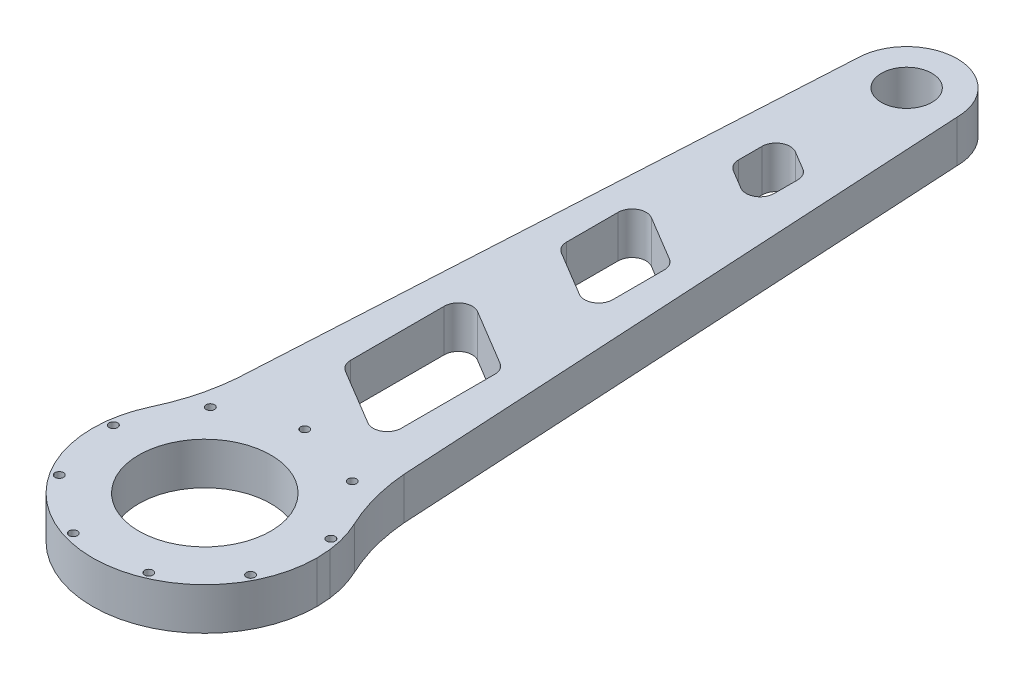
SolidWorks part; units mm, degrees
material "1060 合金"
ref_plane "前视基准面" through (0, 0, 0) normal (0, 0, 1) x (1, 0, 0)
ref_plane "上视基准面" through (0, 0, 0) normal (0, 1, 0) x (1, 0, 0)
ref_plane "右视基准面" through (0, 0, 0) normal (1, 0, 0) x (0, 0, -1)
sketch "草图1" plane through (0, 0, 0) normal (0, 1, 0) x (1, 0, 0)
  line L0 (0, 0) -> (0, 250) construction
  line L1 (-17.9929, -0.504) -> (-24.9902, 249.3)
  line L2 (17.9929, -0.504) -> (24.9902, 249.3)
  line L3 (-11.9953, -0.336) -> (-18.9926, 249.468) construction
  line L4 (11.9953, -0.336) -> (18.9926, 249.468) construction
  line L5 (-16.4444, 158.5) -> (15.7446, 133.5146) construction
  line L6 (15.7446, 133.5146) -> (18.4752, 231) construction
  line L7 (18.4752, 231) -> (-18.0888, 217.2024) construction
  line L8 (-18.0888, 217.2024) -> (-16.4444, 158.5) construction
  line L9 (15.7446, 133.5146) -> (-18.0888, 217.2024) construction
  line L10 (18.5259, 134.639) -> (-15.3075, 218.3268) construction
  line L11 (12.9633, 132.3901) -> (-20.8701, 216.0779) construction
  line L12 (-16.4444, 158.5) -> (-17.7049, 203.5)
  line L13 (-17.7049, 203.5) -> (11.0289, 137.1749)
  line L14 (11.0289, 137.1749) -> (-16.4444, 158.5)
  line L15 (15.9543, 141) -> (18.4752, 231)
  line L16 (-15.3075, 218.3268) -> (-13.7162, 214.3907) construction
  line L17 (18.4752, 231) -> (-12, 219.5)
  line L18 (-12, 219.5) -> (15.9543, 141)
  circle A0 centre (0, 250) radius 25 construction
  circle A1 centre (0, 0) radius 18 construction
  circle A2 centre (0, 0) radius 5.05
  circle A3 centre (0, 250) radius 13
  arc A4 (-17.9929, -0.504) -> (17.9929, -0.504) centre (0, 0) ccw
  arc A5 (-24.9902, 249.3) -> (24.9902, 249.3) centre (0, 250) cw
  arc A6 (-18.9926, 249.468) -> (18.9926, 249.468) centre (0, 250) cw construction
  arc A7 (-11.9953, -0.336) -> (11.9953, -0.336) centre (0, 0) ccw construction
  dimension "D2" = 50
  dimension "D3" = 36
  dimension "D4" = 10.1
  dimension "D5" = 26
  dimension "D1" = 250
  dimension "D9" = 19
  dimension "D10" = 30.5
  dimension "D11" = 16
  dimension "D12" = 45
  dimension "D13" = 90
  dimension "D14" = 12
  dimension "D6" = 6
  dimension "D7" = 3
  dimension "D8" = 3
extrude "凸台-拉伸1" add sketch "草图1" along normal blind 15
fillet "圆角1" radius 3 6 edges at (18.4752, 7.5, -231) (-12, 7.5, -219.5) (-17.7049, 7.5, -203.5) (-16.4444, 7.5, -158.5) (15.9543, 7.5, -141) (11.0289, 7.5, -137.1749)
sketch "草图2" plane through (0, 15, 0) normal (0, 1, 0) x (1, 0, 0)
  line L0 (0, 250) -> (-15, 250) construction
  circle A0 centre (-15, 250) radius 2
  dimension "D2" = 4
  dimension "D1" = 15
extrude "切除-拉伸1" [suppressed] cut sketch "草图2" against normal through all
pattern_circular "阵列(圆周)1" [suppressed] count 3 over 360 reverse direction yes of bodies 107
sketch "草图3" plane through (0, 15, 0) normal (0, 1, 0) x (1, 0, 0)
  line L0 (0, 250) -> (14.25, 250) construction
  circle A0 centre (14.25, 250) radius 2
  dimension "D2" = 4
  dimension "D1" = 14.25
extrude "切除-拉伸2" [suppressed] cut sketch "草图3" against normal through all
pattern_circular "阵列(圆周)2" [suppressed] count 3 over 360 of bodies 109
sketch "草图4" plane through (0, 15, 0) normal (0, 1, 0) x (1, 0, 0)
  line L2 (8.9965, -0.252) -> (15.9937, 249.552)
  line L3 (8.9965, -0.252) -> (15.9937, 249.552) construction
  line L4 (-13.0503, 144.4724) -> (12.4949, 124.6439)
  line L5 (-15.9937, 249.552) -> (-8.9965, -0.252)
  line L6 (-15.9937, 249.552) -> (-8.9965, -0.252) construction
  line L7 (-15.3248, 157.6309) -> (1.7846, 144.3504) construction
  line L8 (12.4949, 124.6439) -> (9.7421, 26.3657)
  line L9 (9.7421, 26.3657) -> (-10.1751, 41.8256)
  line L10 (-10.1751, 41.8256) -> (-13.0503, 144.4724)
  dimension "D3" = 9
  dimension "D1" = 9
  dimension "D2" = 9
extrude "切除-拉伸3" [suppressed] cut sketch "草图4" against normal through all
fillet "圆角2" [suppressed] radius 3
sketch "草图5" plane through (0, 15, 0) normal (0, 1, 0) x (1, 0, 0)
  circle A0 centre (0, 0) radius 27.5
  circle A1 centre (0, 0) radius 5.05
  dimension "D1" = 55
extrude "凸台-拉伸2" [suppressed] add sketch "草图5" against normal up to surface (10 mm away) up to face at (-8.6392, 0, -164.5721)
fillet "圆角3" [suppressed] radius 6
sketch "草图6" [suppressed] plane through (0, 15, 0) normal (0, 1, 0) x (1, 0, 0)
  line L0 (12.4949, 124.6439) -> (-10.1751, 41.8256) construction
  line L1 (-13.0503, 144.4724) -> (-10.1751, 41.8256) construction
  line L2 (9.6014, 125.4359) -> (-13.0687, 42.6176)
  line L3 (15.3885, 123.8518) -> (-7.2816, 41.0335)
  line L4 (-7.2816, 41.0335) -> (-7.6098, 39.8344)
  line L5 (-7.6098, 39.8344) -> (-13.0687, 42.6176)
  line L6 (9.6014, 125.4359) -> (9.9296, 126.6351)
  line L7 (9.9296, 126.6351) -> (15.3885, 123.8518)
  line L8 (-10.1751, 41.8256) -> (9.7421, 26.3657) construction
  line L9 (12.4949, 124.6439) -> (-13.0503, 144.4724) construction
  dimension "D1" = 3
  dimension "D2" = 3
extrude "凸台-拉伸3" [suppressed] add sketch "草图6" against normal up to surface (15 mm away) up to face at (-8.6392, 0, -164.5721)
fillet "圆角4" [suppressed] radius 3
sketch "草图7" plane through (0, 15, 0) normal (0, 1, 0) x (1, 0, 0)
  line L1 (15, 15) -> (-15, 15) construction
  line L2 (15, 15) -> (15, -15) construction
  line L3 (15, -15) -> (-15, -15) construction
  line L4 (-15, 15) -> (-15, -15) construction
  circle A0 centre (0, 0) radius 5.05 construction
  circle A1 centre (15, 15) radius 2.05
  circle A2 centre (-15, 15) radius 2.05
  circle A3 centre (-15, -15) radius 2.05
  circle A5 centre (15, -15) radius 2.05
  dimension "D2" = 15
  dimension "D4" = 4.1
  dimension "D1" = 30
  dimension "D3" = 15
extrude "切除-拉伸4" cut sketch "草图7" against normal through all
sketch "草图8" plane through (0, 15, 0) normal (0, 1, 0) x (1, 0, 0)
  circle A0 centre (0, 0) radius 13
  dimension "D1" = 26
extrude "切除-拉伸5" cut sketch "草图8" against normal through all
sketch "草图9" plane through (0, 15, 0) normal (0, 1, 0) x (1, 0, 0)
  circle A0 centre (0, 0) radius 25
  circle A1 centre (0, 0) radius 13
  circle A2 centre (0, 0) radius 13 construction
  dimension "D1" = 50
extrude "凸台-拉伸4" add sketch "草图9" against normal up to surface (15 mm away) up to face at (0, 0, 13)
sketch "草图10" plane through (0, 15, 0) normal (0, 1, 0) x (1, 0, 0)
  line L0 (-40, 0) -> (-24.9902, 249.3)
  line L2 (-24.9902, 249.3) -> (-18.9931, 35.2031)
  line L3 (24.9902, 249.3) -> (18.9931, 35.2031)
  line L4 (40, 0) -> (24.9902, 249.3)
  arc A0 (18.9931, 35.2031) -> (-18.9931, 35.2031) centre (0, 0) ccw
  circle A3 centre (22.6316, 29.9009) radius 1.5
  circle A4 centre (36.5567, 8.3581) radius 1.5
  circle A5 centre (33.3766, -17.0955) radius 1.5
  circle A6 centre (14.5791, -34.5499) radius 1.5
  circle A7 centre (-11.04, -35.8381) radius 1.5
  circle A8 centre (-31.4934, -20.3572) radius 1.5
  circle A9 centre (-37.2107, 4.6491) radius 1.5
  circle A10 centre (-25.5167, 27.48) radius 1.5
  circle A11 centre (-1.8831, 37.4527) radius 1.5
  circle A12 centre (0, 0) radius 21.5
  arc A13 (-39.711, 4.7992) -> (39.711, 4.7992) centre (0, 0) ccw
  line M3 (-24.9902, 249.3) -> (-18.4787, 16.8385)
  arc M4 (-18.4787, 16.8385) -> (18.4787, 16.8385) centre (0, 0) ccw
  line M5 (18.4787, 16.8385) -> (24.9902, 249.3)
  dimension "D1" = 9
  dimension "D2" = 37.5
extrude "凸台-拉伸5" add sketch "草图10" against normal up to surface (15 mm away) contours L0 A13 L4 A3 A4 A5 A6 A7 A8 A9 A10 M5 M4 M3 region at (-36.8594, 15, -2.2192) up to face at (-8.6392, 0, -164.5721)
sketch "草图12" plane through (0, 15, 0) normal (0, 1, 0) x (1, 0, 0)
  circle A0 centre (0, 0) radius 20.8885
  circle A1 centre (-1.8831, 37.4527) radius 1.5
sketch "草图14" plane through (0, 15, 0) normal (0, 1, 0) x (1, 0, 0)
  circle A0 centre (0, 250) radius 13
  circle A2 centre (0, 250) radius 9
extrude "凸台-拉伸6" add sketch "草图14" against normal up to surface (15 mm away) up to face at (0, 0, -121.075)
sketch "草图13" plane through (0, 15, 0) normal (0, 1, 0) x (1, 0, 0)
  circle A8 centre (0, 0) radius 23.5
  circle A9 centre (-1.8831, 37.4527) radius 1.5
  point P22 (14.0279, 72.2285)
  point P30 (-14.6515, 94.4897)
  circle M28 centre (0, 0) radius 13
extrude "切除-拉伸6" cut sketch "草图13" against normal blind 25 contours A8 M28 | A9 | A9 region at (-22.8353, 15, 0) region at (-1.8831, 15, -37.4527)
sketch "草图15" plane through (0, 15, 0) normal (0, 1, 0) x (1, 0, 0)
  line L3 (25, 250) -> (39.713, 4.7828)
  line L4 (-40, 0) -> (-25, 250)
  line L5 (18, 250) -> (29.6849, 41.272)
  line L6 (-18, 250) -> (-29.6848, 41.272)
  arc A10 (29.6849, 41.272) -> (36.1634, 17.0941) centre (99.4494, 47.0087) ccw
  arc A11 (-36.1634, 17.0941) -> (-29.6848, 41.272) centre (-99.4494, 47.0088) ccw
  arc A14 (-36.1634, 17.0941) -> (-40, 0) centre (0, 0) ccw
  arc A15 (39.713, 4.7828) -> (36.1634, 17.0941) centre (0, 0) ccw
  arc A16 (18, 250) -> (-18, 250) centre (0, 250) ccw
  arc A18 (25, 250) -> (-25, 250) centre (0, 250) ccw
  line M18 (40, 0) -> (24.9902, 249.3)
  arc M19 (24.9902, 249.3) -> (-24.9902, 249.3) centre (0, 250) ccw
  line M20 (-24.9902, 249.3) -> (-40, 0)
  arc M31 (14.2921, 229.4215) -> (18.3501, 226.5306) centre (15.3512, 226.6146) cw
  line M32 (18.3501, 226.5306) -> (16.403, 157.0198)
  dimension "D1" = 70
extrude "切除-拉伸7" cut sketch "草图15" against normal blind 20 contours A16 A10 A15 A14 A11 M31 M32 M18 M19 M20 region at (22.1815, 15, -249.6894)
sketch "草图18" plane through (0, 0, 0) normal (0, -1, 0) x (-1, 0, 0)
  line L0 (-20.8682, 131.8446) -> (20.7069, 152.0972)
  line L1 (20.7069, 152.0972) -> (16.906, 230.5917)
  line L2 (16.906, 230.5917) -> (-18.5103, 232.6034)
  line L3 (-18.5103, 232.6034) -> (-19.3366, 196.0291)
  line L4 (-19.3366, 196.0291) -> (-20.8682, 131.8446)
extrude "凸台-拉伸9" add sketch "草图18" against normal up to surface (15 mm away) up to face at (0, 15, 23.5)
sketch "草图19" plane through (0, 15, 0) normal (0, 1, 0) x (1, 0, 0)
  line L9 (0, 241) -> (0, 55.122) construction
  line L12 (-7.7143, 206.182) -> (-7.7143, 197.8351)
  line L14 (-0.1472, 210.4727) -> (6.5671, 206.4556)
  line L15 (-5.2814, 193.5444) -> (1.4329, 189.5273)
  line L24 (9, 250) -> (9, 49.7374) construction
  line L25 (-7.7143, 245.3643) -> (-7.7143, 59.7374) construction
  line L28 (9, 202.1649) -> (9, 193.818)
  line L31 (-13, 62.8998) -> (-13, 169.0296) construction
  line L32 (13, 47.3442) -> (13, 174.663) construction
  line L33 (-13, 160.2116) -> (-13, 141.8647)
  line L34 (-5.4329, 164.5023) -> (10.5671, 154.9296)
  line L35 (-10.5671, 137.574) -> (5.4329, 128.0014)
  line L36 (13, 150.6389) -> (13, 132.2921)
  line L37 (-15, 100.2783) -> (-15, 66.9314)
  line L38 (-7.4329, 104.569) -> (12.5671, 92.6032)
  line L39 (-12.5671, 62.6407) -> (7.4329, 50.6749)
  line L40 (15, 88.3125) -> (15, 54.9656)
  circle A7 centre (0, 250) radius 9 construction
  arc A9 (6.5671, 206.4556) -> (9, 202.1649) centre (4, 202.1649) cw
  arc A10 (-7.7143, 197.8351) -> (-5.2814, 193.5444) centre (-2.7143, 197.8351) ccw
  arc A11 (-7.7143, 206.182) -> (-0.1472, 210.4727) centre (-2.7143, 206.182) cw
  arc A12 (9, 193.818) -> (1.4329, 189.5273) centre (4, 193.818) cw
  arc A13 (-13, 160.2116) -> (-5.4329, 164.5023) centre (-8, 160.2116) cw
  arc A14 (-13, 141.8647) -> (-10.5671, 137.574) centre (-8, 141.8647) ccw
  arc A15 (10.5671, 154.9296) -> (13, 150.6389) centre (8, 150.6389) cw
  arc A16 (13, 132.2921) -> (5.4329, 128.0014) centre (8, 132.2921) cw
  arc A17 (-15, 100.2783) -> (-7.4329, 104.569) centre (-10, 100.2783) cw
  arc A18 (-15, 66.9314) -> (-12.5671, 62.6407) centre (-10, 66.9314) ccw
  arc A19 (12.5671, 92.6032) -> (15, 88.3125) centre (10, 88.3125) cw
  arc A20 (15, 54.9656) -> (7.4329, 50.6749) centre (10, 54.9656) cw
  point P14 (9, 205)
  point P22 (-7.7143, 195)
  point P25 (-7.7143, 215)
  point P39 (9, 185)
  point P42 (13, 141.4655)
  point P46 (-13, 139.0296)
  point P49 (13, 153.474)
  point P52 (13, 123.474)
  point P55 (-15, 109.0963)
  point P60 (15, 91.1476)
  point P63 (15, 46.1476)
  dimension "D2" = 0
  dimension "D1" = 20
  dimension "D14" = 5
  dimension "D3" = 26
  dimension "D4" = 25
  dimension "D5" = 35
  dimension "D6" = 45
  dimension "D7" = 30
  dimension "D8" = 13
  dimension "D9" = 0
  dimension "D10" = 45
  dimension "D11" = 30
  dimension "D12" = 15
  dimension "D13" = 30
extrude "切除-拉伸8" cut sketch "草图19" against normal blind 30
